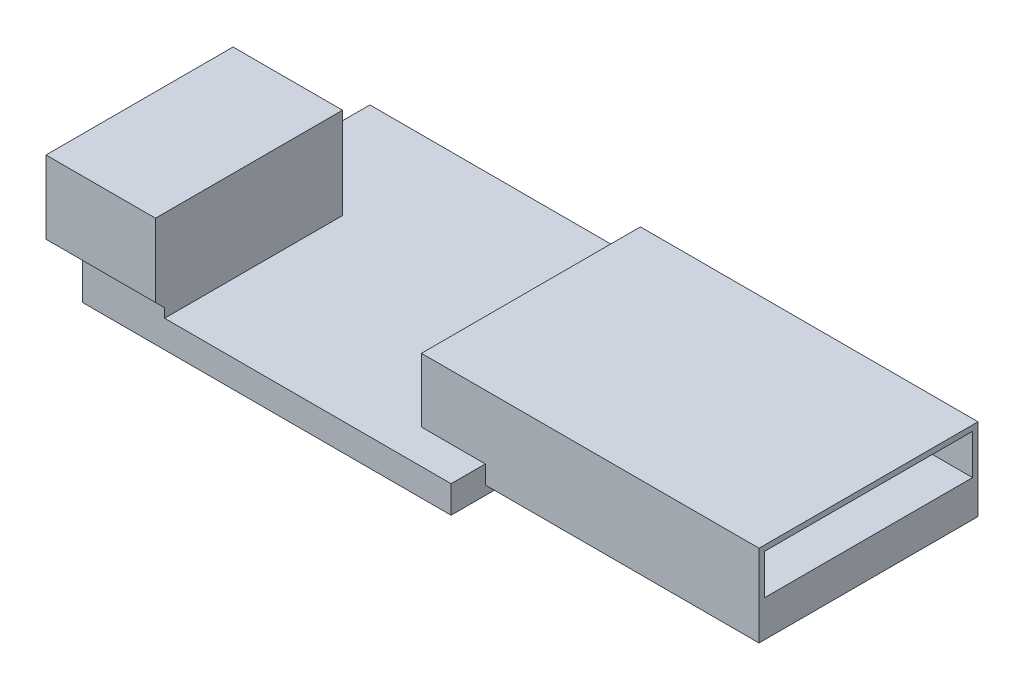
SolidWorks part; units mm, degrees
ref_plane "Plan de face" through (0, 0, 0) normal (0, 0, 1) x (1, 0, 0)
ref_plane "Plan de dessus" through (0, 0, 0) normal (0, 1, 0) x (1, 0, 0)
ref_plane "Plan de droite" through (0, 0, 0) normal (1, 0, 0) x (0, 0, -1)
sketch "Esquisse1" plane through (0, 0, 0) normal (0, 1, 0) x (1, 0, 0)
  line L1 (0, 0) -> (-20.2, 0)
  line L2 (0, 0) -> (0, 15.75)
  line L3 (0, 15.75) -> (-20.2, 15.75)
  line L4 (-20.2, 0) -> (-20.2, 15.75)
  dimension "D1" = 15.75
  dimension "D2" = 20.2
extrude "Boss.-Extru.1" add sketch "Esquisse1" along normal blind 1.5
sketch "Esquisse2" plane through (0, 1.5, 0) normal (0, 1, 0) x (1, 0, 0)
  line L0 (0, 0) -> (0, 15.75) construction
  line L1 (-3.5, 13.875) -> (15, 13.875)
  line L2 (-3.5, 13.875) -> (-3.5, 1.875)
  line L3 (-3.5, 1.875) -> (15, 1.875)
  line L4 (15, 13.875) -> (15, 1.875)
  line L5 (-3.5, 7.875) -> (0, 7.875) construction
  dimension "D1" = 12
  dimension "D2" = 18.5
  dimension "D3" = 3.5
extrude "Boss.-Extru.2" add sketch "Esquisse2" along normal blind 3.5 and the other way blind 1
sketch "Esquisse3" plane through (15, 0, 0) normal (1, 0, 0) x (0, 0, -1)
  line L0 (1.875, 5) -> (13.875, 5) construction
  line L1 (2.175, 4.7) -> (13.575, 4.7)
  line L2 (2.175, 4.7) -> (2.175, 2.5)
  line L3 (2.175, 2.5) -> (13.575, 2.5)
  line L4 (13.575, 4.7) -> (13.575, 2.5)
  line L5 (13.875, 0.5) -> (13.875, 5) construction
  line L6 (1.875, 0.5) -> (1.875, 5) construction
  line L7 (1.875, 0.5) -> (13.875, 0.5) construction
  dimension "D1" = 0.3
  dimension "D2" = 0.3
  dimension "D3" = 0.3
  dimension "D4" = 2
extrude "Enlèv. mat.-Extru.1" cut sketch "Esquisse3" against normal blind 13.5
sketch "Esquisse4" plane through (0, 1.5, 0) normal (0, 1, 0) x (1, 0, 0)
  line L0 (-20.2, 0) -> (0, 0) construction
  line L1 (-15.7, -0.5) -> (-21.7, -0.5)
  line L2 (-15.7, -0.5) -> (-15.7, 9.75)
  line L3 (-15.7, 9.75) -> (-21.7, 9.75)
  line L4 (-21.7, -0.5) -> (-21.7, 9.75)
  line L5 (-20.2, 15.75) -> (-20.2, 0) construction
  dimension "D1" = 6
  dimension "D2" = 10.25
  dimension "D3" = 0.5
  dimension "D4" = 4.5
extrude "Boss.-Extru.4" add sketch "Esquisse4" along normal blind 5
chamfer "Chanfrein1" distance 1 angle 45 1 edges at (-18.7, 1.5, 0.5)
